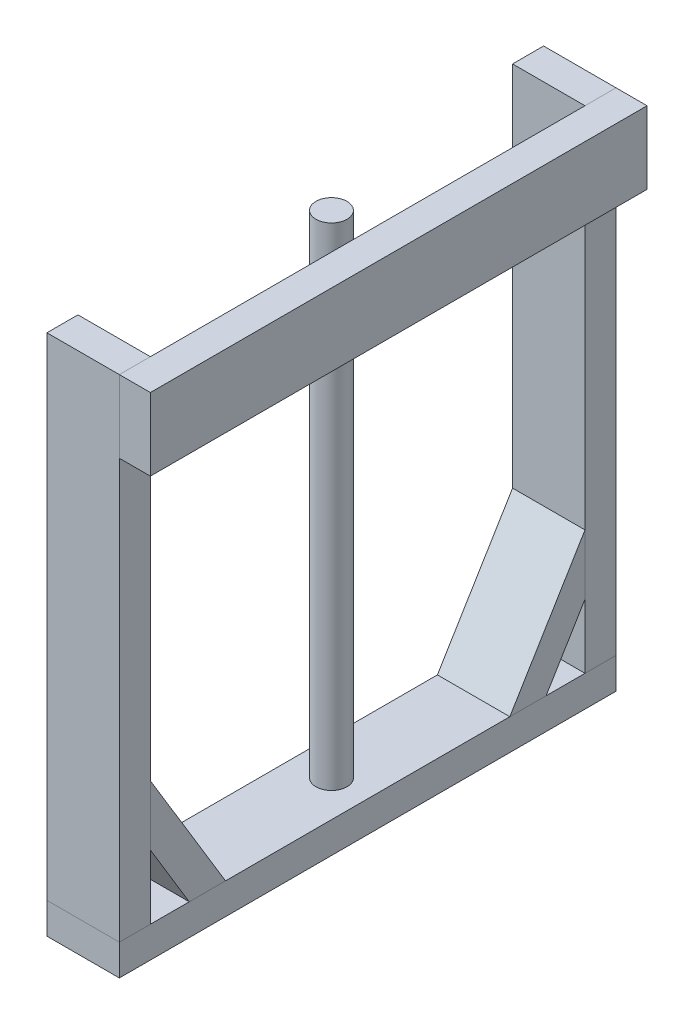
SolidWorks part; units mm, degrees
ref_plane "Front Plane" through (0, 0, 0) normal (0, 0, 1) x (1, 0, 0)
ref_plane "Top Plane" through (0, 0, 0) normal (0, 1, 0) x (1, 0, 0)
ref_plane "Right Plane" through (0, 0, 0) normal (1, 0, 0) x (0, 0, -1)
sketch "Sketch1" plane through (0, 0, 0) normal (1, 0, 0) x (0, 0, -1)
  line L1 (-304.8, 0) -> (304.8, 0)
  line L2 (-304.8, 0) -> (-304.8, -88.9)
  line L3 (-304.8, -88.9) -> (304.8, -88.9)
  line L4 (304.8, 0) -> (304.8, -88.9)
  dimension "D1" = 609.6
  dimension "D2" = 88.9
extrude "Top_Cross_Support" add sketch "Sketch1" along normal blind 38.1
sketch "Sketch2" plane through (0, 0, 0) normal (-1, 0, 0) x (0, 0, 1)
  line L1 (304.8, 0) -> (266.7, 0)
  line L2 (304.8, 0) -> (304.8, -603.25)
  line L3 (304.8, -603.25) -> (266.7, -603.25)
  line L4 (266.7, 0) -> (266.7, -603.25)
  dimension "D1" = 603.25
  dimension "D2" = 38.1
extrude "Leg" add sketch "Sketch2" along normal blind 88.9 separate body
mirror "Leg_Mirror" about plane through (0, 0, 0) normal (0, 0, 1) of bodies 102
sketch "Sketch4" plane through (0, -603.25, 0) normal (0, -1, 0) x (1, 0, 0)
  line L1 (0, 304.8) -> (-88.9, 304.8)
  line L2 (0, 304.8) -> (0, -304.8)
  line L3 (0, -304.8) -> (-88.9, -304.8)
  line L4 (-88.9, 304.8) -> (-88.9, -304.8)
extrude "Bottom_Cross_Support" add sketch "Sketch4" along normal blind 38.1 separate body
sketch "Sketch5" plane through (0, 0, 0) normal (1, 0, 0) x (0, 0, -1)
  line L0 (-218.9815, -603.25) -> (-266.7, -524.4223)
  line L1 (304.8, -603.25) -> (-304.8, -603.25) construction
  line L2 (-266.7, 0) -> (-266.7, -603.25) construction
  line L3 (-266.7, -450.85) -> (-174.4444, -603.25)
  line L4 (-174.4444, -603.25) -> (-218.9815, -603.25)
  line L5 (-266.7, -524.4223) -> (-266.7, -450.85)
  dimension "D1" = 38.1
  dimension "D2" = 152.4
extrude "Low_Diagonal_Support" add sketch "Sketch5" against normal blind 88.9 separate body
mirror "Low_Diagonal_Support_Mirror" about plane through (0, 0, 0) normal (0, 0, 1) of bodies 106
sketch "Sketch6" plane through (0, -603.25, 0) normal (0, 1, 0) x (1, 0, 0)
  line L0 (-88.9, -304.8) -> (-88.9, 304.8) construction
  line L1 (0, 304.8) -> (0, -304.8) construction
  line L2 (0, 0) -> (-88.9, 0) construction
  circle A0 centre (-44.45, 0) radius 19.05
  dimension "D1" = 38.1
extrude "Actuator" add sketch "Sketch6" along normal blind 603.25 separate body
equation "\"height\"=23.75"
equation "\"D1@Sketch2\"=\"height\""
equation "\"D1@Actuator\"=\"height\""
